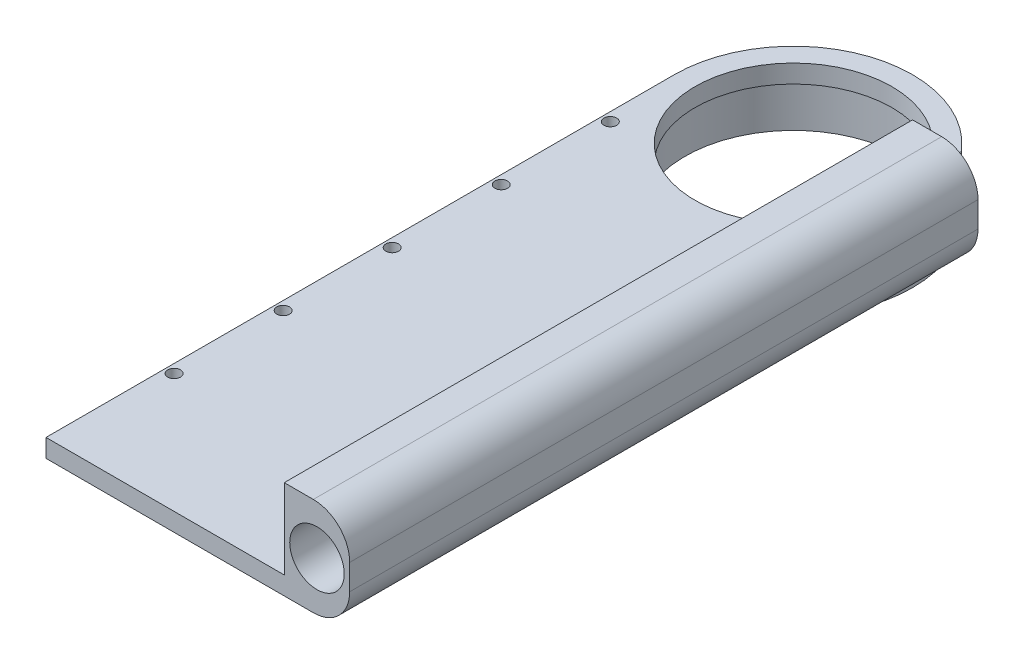
SolidWorks part; units mm, degrees
ref_plane "Front Plane" through (0, 0, 0) normal (0, 0, 1) x (1, 0, 0)
ref_plane "Top Plane" through (0, 0, 0) normal (0, 1, 0) x (1, 0, 0)
ref_plane "Right Plane" through (0, 0, 0) normal (1, 0, 0) x (0, 0, -1)
sketch "Sketch1" plane through (0, 0, 0) normal (0, 1, 0) x (1, 0, 0)
  line L5 (-32.774, -22.3805) -> (-32.774, 177.6195)
  line L6 (32.774, -22.3805) -> (32.774, 177.6195)
  circle A3 centre (0, 177.6195) radius 4.5
  circle A4 centre (0, 67.6378) radius 4.5
  circle A7 centre (-6.7334, 37.1195) radius 1.25
  circle A8 centre (-6.7334, 27.6195) radius 1.25
  circle A14 centre (0, 53.6052) radius 1.75
  circle A15 centre (-14.0327, 67.6378) radius 1.75
  circle A16 centre (0, 81.6705) radius 1.75
  circle A17 centre (14.0327, 67.6378) radius 1.75
  circle A18 centre (0, 67.6378) radius 11.5
  circle A19 centre (0, 67.6378) radius 4.5
  arc A22 (32.774, -22.3805) -> (-32.774, -22.3805) centre (0, -22.3805) cw
  arc A23 (32.774, 177.6195) -> (-32.774, 177.6195) centre (0, 177.6195) ccw
  circle A25 centre (0, -9.3805) radius 2.75
  circle A27 centre (11.2583, -15.8805) radius 2.75
  circle A28 centre (11.2583, -28.8805) radius 2.75
  circle A29 centre (0, -35.3805) radius 2.75
  circle A30 centre (-11.2583, -28.8805) radius 2.75
  circle A31 centre (-11.2583, -15.8805) radius 2.75
  dimension "D1" = 13
  dimension "D2" = 200
  dimension "D3" = 50
  dimension "D4" = 109.9817
  dimension "D8" = 9.5
extrude "Boss-Extrude10" add sketch "Sketch1" against normal blind 5 contours L6 A23 L5 A22 A31 A30 A29 A28 A27 A25 A3 A7 A8 A14 A15 A16 A17 A18 | A18 | A19 region at (-30.0388, 0, -77.6195)
sketch "Sketch2" plane through (0, 0, 0) normal (0, -1, 0) x (1, 0, 0)
  line L30 (28, -177.6198) -> (28, -97.6193)
  line L31 (-28, -4.769) -> (-32.774, -4.769)
  line L35 (-28, -177.6198) -> (-28, -97.62)
  line L46 (-28, -4.769) -> (28, -4.769)
  line L53 (28, -4.769) -> (32.774, -4.769)
  line L54 (-32.774, 22.3805) -> (-32.774, -177.6198)
  line L55 (32.774, 22.3805) -> (32.774, -177.6198)
  line L56 (-28, 22.3805) -> (-28, -97.62)
  line L57 (28, -97.6193) -> (28, 22.3805)
  circle A4 centre (-18, -157.4003) radius 1.75
  circle A5 centre (18.0605, -157.4003) radius 1.75
  circle A6 centre (-18, -97.6199) radius 1.75
  circle A7 centre (18.0032, -97.4003) radius 1.75
  arc A15 (28, -177.6198) -> (-28, -177.6198) centre (0, -177.6198) cw
  arc A26 (32.774, 22.3805) -> (-32.774, 22.3805) centre (0, 22.3805) ccw
  arc A28 (-32.774, -177.6198) -> (32.774, -177.6198) centre (0, -177.6198) ccw
  arc A29 (28, 22.3805) -> (-28, 22.3805) centre (0, 22.3805) ccw
  dimension "D1" = 60
extrude "Boss-Extrude11" add sketch "Sketch1<16>" against normal blind 5 contours A7 | A8 region at (-6.7334, 0, -37.1195) region at (-6.7334, 0, -27.6195)
sketch "Sketch1<16>" plane through (0, 0, 0) normal (0, 1, 0) x (1, 0, 0) same geometry as "Sketch1"
sketch "Sketch3" plane through (0, -5, 0) normal (0, -1, 0) x (1, 0, 0)
  line L2 (-32.774, 22.3805) -> (-32.774, -177.6195) construction
  circle A4 centre (15, -102.0563) radius 1.75
  circle A6 centre (-30.384, -67.6195) radius 1.75
  circle A7 centre (-30.384, -37.6195) radius 1.75
  arc A8 (32.774, 22.3805) -> (-32.774, 22.3805) centre (0, 22.3805) ccw construction
  circle A9 centre (-30.384, -97.6195) radius 1.75
  circle A10 centre (-30.384, -127.6195) radius 1.75
  circle A11 centre (-30.384, -157.6195) radius 1.75
  circle A13 centre (30.384, -157.6195) radius 1.75
  circle A14 centre (30.384, -127.6195) radius 1.75
  circle A15 centre (30.384, -97.6195) radius 1.75
  circle A16 centre (30.384, -67.6195) radius 1.75
  circle A17 centre (30.384, -37.6195) radius 1.75
  dimension "D1" = 60
  dimension "D2" = 2.39
  dimension "D3" = 5
extrude "Cut-Extrude5" cut sketch "Sketch3" against normal blind 17
extrude "Cut-Extrude7" cut sketch "Sketch2" along normal blind 10 contours A29 L57 L53 L55 A26 L54 L31 L56 | L57 A29 L56 L46 region at (28.8881, 0, 8.8057) region at (0, 0, 20.1987)
extrude "Boss-Extrude12" add sketch "Sketch1<18>" against normal blind 5 contours A4 | A17 | A16 | A14 | A15 region at (0, 0, -67.6378) region at (0, 0, -53.6052) region at (-14.0327, 0, -67.6378) region at (0, 0, -81.6705) region at (14.0327, 0, -67.6378)
sketch "Sketch1<18>" plane through (0, 0, 0) normal (0, 1, 0) x (1, 0, 0) same geometry as "Sketch1"
sketch "Sketch5" plane through (0, -5, 0) normal (0, -1, 0) x (1, 0, 0)
  text T0 "<b>       JN V1</b>" font "Century Gothic" height in points 72
sketch "Sketch10" plane through (0, -5, 0) normal (0, -1, 0) x (1, 0, 0)
  circle A0 centre (0, -177.6195) radius 29.85
  circle A1 centre (0, -177.6195) radius 32.768
extrude "Boss-Extrude13" add sketch "Sketch10" along normal blind 13
sketch "Sketch11" plane through (0, -5, 0) normal (0, -1, 0) x (1, 0, 0)
  circle A0 centre (0, -177.6195) radius 27.095
extrude "Cut-Extrude8" cut sketch "Sketch11" against normal blind 13
extrude "Boss-Extrude14" add sketch "Sketch5" along normal blind 3
sketch "Sketch13" plane through (0, -5, 0) normal (0, -1, 0) x (1, 0, 0)
  line L1 (-5.999, -121.1011) -> (6.001, -121.1011)
  line L2 (-5.999, -121.1011) -> (-5.999, -125.1011)
  line L3 (-5.999, -125.1011) -> (6.001, -125.1011)
  line L4 (6.001, -121.1011) -> (6.001, -125.1011)
  line L5 (-5.999, -121.1011) -> (6.001, -125.1011) construction
  line L6 (-5.999, -125.1011) -> (6.001, -121.1011) construction
  line L8 (-32.774, -4.769) -> (-32.774, -177.6195) construction
  point P0 (0.001, -123.1011)
  dimension "D1" = 12
  dimension "D2" = 26.775
extrude "Boss-Extrude15" add sketch "Sketch13" along normal blind 25
sketch "Sketch14" plane through (0, 0, -125.1011) normal (0, 0, -1) x (-1, 0, 0)
  line L2 (5.999, -30) -> (-6.001, -30) construction
  circle A0 centre (0, -22.5) radius 1.25
  circle A1 centre (0, -13) radius 1.25
  dimension "D1" = 7.5
  dimension "D2" = 9.5
extrude "Cut-Extrude9" cut sketch "Sketch14" against normal blind 25
fillet "Fillet1" radius 2.5 4 edges at (6.001, -30, -123.1011) (-5.999, -30, -123.1011) (-5.999, -5, -123.1011) (6.001, -5, -123.1011)
sketch "Sketch15" plane through (-32.774, 0, 0) normal (-1, 0, 0) x (0, 0, 1)
  line L1 (-177.6195, 0) -> (-4.769, 0)
  line L2 (-177.6195, 0) -> (-177.6195, -5)
  line L3 (-177.6195, -5) -> (-4.769, -5)
  line L4 (-4.769, 0) -> (-4.769, -5)
extrude "Boss-Extrude16" [suppressed] add sketch "Sketch15" along normal blind 18
sketch "Sketch16" [suppressed] plane through (0, 0, 0) normal (0, 1, 0) x (1, 0, 0)
  line L1 (-50.774, 4.769) -> (-32.774, 4.769)
  line L2 (-50.774, 4.769) -> (-50.774, 177.6195)
  line L3 (-50.774, 177.6195) -> (-32.774, 177.6195)
  line L4 (-32.774, 4.769) -> (-32.774, 177.6195)
extrude "Boss-Extrude17" [suppressed] add sketch "Sketch16" along normal blind 22
sketch "Sketch17" [suppressed] plane through (0, 0, -177.6195) normal (0, 0, -1) x (-1, 0, 0)
  circle A0 centre (41.774, 8.5) radius 7.5
extrude "Cut-Extrude10" [suppressed] cut sketch "Sketch17" against normal blind 176
fillet "Fillet2" [suppressed] radius 10
sketch "Sketch18" plane through (32.774, 0, 0) normal (1, 0, 0) x (0, 0, -1)
  line L0 (144.8516, -5) -> (210.3875, -5) construction
  line L1 (4.769, 0) -> (177.6195, 0)
  line L2 (4.769, 0) -> (4.769, -5)
  line L3 (4.769, -5) -> (177.6195, -5)
  line L4 (177.6195, 0) -> (177.6195, -5)
extrude "Boss-Extrude18" add sketch "Sketch18" along normal blind 18
sketch "Sketch19" plane through (0, 0, 0) normal (0, 1, 0) x (1, 0, 0)
  line L1 (32.774, 177.6195) -> (50.774, 177.6195)
  line L2 (32.774, 177.6195) -> (32.774, 4.769)
  line L3 (32.774, 4.769) -> (50.774, 4.769)
  line L4 (50.774, 177.6195) -> (50.774, 4.769)
extrude "Boss-Extrude19" add sketch "Sketch19" along normal blind 22
sketch "Sketch20" plane through (0, 0, -177.6195) normal (0, 0, -1) x (-1, 0, 0)
  circle A0 centre (-41.774, 8.5) radius 7.5
extrude "Cut-Extrude11" cut sketch "Sketch20" against normal blind 208
fillet "Fillet3" radius 10 2 edges at (50.774, -5, -91.1943) (50.774, 22, -91.1943)
